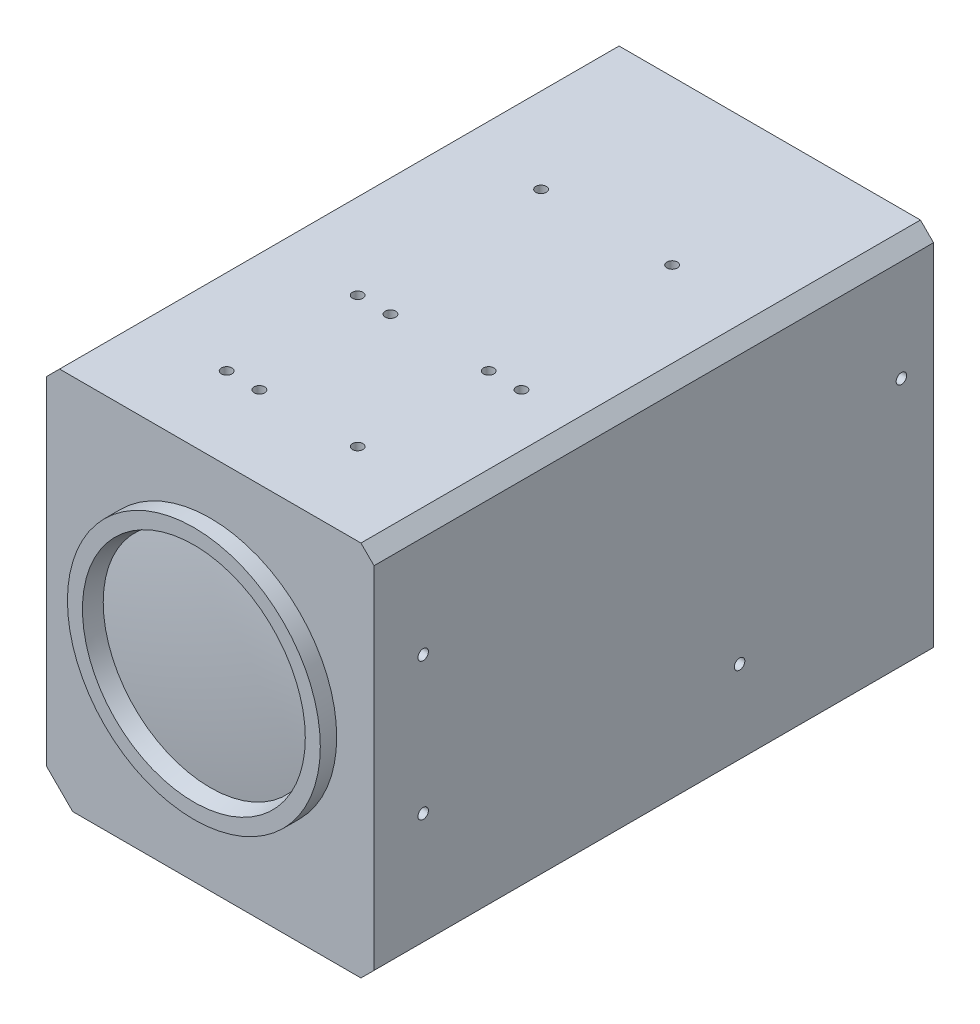
SolidWorks part; units mm, degrees
ref_plane "Front Plane" through (0, 0, 0) normal (0, 0, 1) x (1, 0, 0)
ref_plane "Top Plane" through (0, 0, 0) normal (0, 1, 0) x (1, 0, 0)
ref_plane "Right Plane" through (0, 0, 0) normal (1, 0, 0) x (0, 0, -1)
sketch "Sketch1" plane through (0, 0, 0) normal (0, 0, 1) x (1, 0, 0)
  line L0 (-25, 25.5) -> (-23, 27.5)
  line L1 (-21, -30) -> (23, -30)
  line L2 (-25, -26) -> (-25, 25.5)
  line L3 (-23, 27.5) -> (23, 27.5)
  line L4 (25, -28) -> (25, 25.5)
  line L5 (23, 27.5) -> (25, 25.5)
  line L6 (23, -30) -> (25, -28)
  line L7 (-25, -26) -> (-21, -30)
  point P0 (0, 0)
  point P1 (25, 27.5)
  point P2 (-25, -30)
  point P3 (-25, 27.5)
  point P4 (25, -30)
  dimension "D1" = 57.5
  dimension "D2" = 50
  dimension "D3" = 30
  dimension "D4" = 25
extrude "Boss-Extrude1" add sketch "Sketch1" along normal blind 85.4
sketch "Sketch2" plane through (0, 0, 85.4) normal (0, 0, 1) x (1, 0, 0)
  circle A0 centre (0, 0) radius 19.3
  circle A1 centre (0, 0) radius 17.008
  dimension "D1" = 38.6
  dimension "D2" = 34.016
extrude "Boss-Extrude2" add sketch "Sketch2" along normal blind 2.5
draft "Draft1" type of draft neutral plane draft angle 15 faces to draft 1 face at (17.008, 0, 87.9) neutral plane through (0, 0, 87.9) neutral plane normal (0, 0, 1) parameters "D1"=15
dome "Dome1" faces to dome 1 distance 1 reverse direction no elliptical dome no face at (-16.3381, 0, 85.4) parameters "D1"=1
hole_wizard "1/4 Clearance Hole1" positions "Sketch5" profile "Sketch4" hole size "1/4" standard "Ansi Inch"
sketch "Sketch5" plane through (0, -30, 0) normal (0, -1, 0) x (1, 0, 0)
  line L0 (25, 85.4) -> (25, 0) construction
  line L1 (19.3, 87.9) -> (-19.3, 87.9) construction
  point P0 (0, 67.9)
  dimension "D1" = 25
  dimension "D2" = 20
sketch "Sketch4" plane through (0, -30, 67.9) normal (1, 0, 0) x (0, 0, -1)
  line L0 (0, 0) -> (0, 10.0298)
  line L1 (0, 10.0298) -> (3.3782, 8)
  line L2 (3.3782, 8) -> (3.3782, 0)
  line L5 (3.3782, 0) -> (0, 0)
  line L10 (0, 10.0298) -> (-3.3782, 8) construction
  line L11 (0, -6.35) -> (0, 107.95) construction
  dimension "Hole Dia." = 6.7564
  dimension "Hole Depth" = 8
  dimension "Drill Angle" = 118
hole_wizard "M2x0.4 Tapped Hole1" positions "Sketch7" profile "Sketch6" tap size "M2x0.4" standard "ANSI Metric"
sketch "Sketch7" plane through (0, -30, 0) normal (0, -1, 0) x (-1, 0, 0)
  line L0 (0, -85.4) -> (0, 0) construction
  line L2 (21, -85.4) -> (-23, -85.4) construction
  line L3 (21, 0) -> (-23, 0) construction
  line L4 (-19.3, -87.9) -> (19.3, -87.9) construction
  point P12 (-8, -51.9)
  point P14 (8, -51.9)
  point P16 (-8, -22.9)
  point P18 (8, -22.9)
  point P24 (13.5, -47.7)
  point P26 (-13.5, -47.7)
  point P28 (-13.5, -14.7)
  point P30 (13.5, -14.7)
  dimension "D1" = 16
  dimension "D2" = 29
  dimension "D3" = 36
  dimension "D4" = 8
  dimension "D5" = 27
  dimension "D6" = 13.5
  dimension "D7" = 40.2
  dimension "D8" = 33
sketch "Sketch6" plane through (8, -30, 51.9) normal (1, 0, 0) x (0, 0, -1)
  line L0 (0, 0) -> (0, 2.4807)
  line L1 (0, 2.4807) -> (0.8, 2)
  line L2 (0.8, 2) -> (0.8, 0)
  line L5 (0.8, 0) -> (0, 0)
  line L10 (0, 2.4807) -> (-0.8, 2) construction
  line L11 (0, -6.35) -> (0, 107.95) construction
  dimension "Tap Drill Dia." = 1.6
  dimension "Tap Drill Depth" = 2
  dimension "Drill Angle" = 118
hole_wizard "M2x0.4 Tapped Hole2" positions "Sketch9" profile "Sketch8" tap size "M2x0.4" standard "ANSI Metric"
sketch "Sketch9" plane through (25, 0, 0) normal (1, 0, 0) x (0, 0, -1)
  line L0 (-87.9, 0) -> (0, 0) construction
  line L1 (-87.9, 19.3) -> (-87.9, -19.3) construction
  line L3 (0, -28) -> (0, 25.5) construction
  point P0 (-77.9, 10)
  point P2 (-77.9, -11)
  point P4 (-4.9, 10)
  point P6 (-29.6, -15.4)
  dimension "D1" = 21
  dimension "D2" = 10
  dimension "D3" = 25.4
  dimension "D4" = 48.3
  dimension "D5" = 73
  dimension "D6" = 10
sketch "Sketch8" plane through (25, 10, 77.9) normal (0, 1, 0) x (0, 0, -1)
  line L0 (0, 0) -> (0, 3.6807)
  line L1 (0, 3.6807) -> (0.8, 3.2)
  line L2 (0.8, 3.2) -> (0.8, 0)
  line L5 (0.8, 0) -> (0, 0)
  line L10 (0, 3.6807) -> (-0.8, 3.2) construction
  line L11 (0, -6.35) -> (0, 107.95) construction
  dimension "Tap Drill Dia." = 1.6
  dimension "Tap Drill Depth" = 3.2
  dimension "Drill Angle" = 118
hole_wizard "M2x0.4 Tapped Hole3" positions "Sketch11" profile "Sketch10" tap size "M2x0.4" standard "ANSI Metric"
sketch "Sketch11" plane through (0, 27.5, 0) normal (0, 1, 0) x (1, 0, 0)
  line L0 (0, 0) -> (0, -87.9) construction
  line L1 (-19.3, -87.9) -> (19.3, -87.9) construction
  point P0 (-5, -72.9)
  point P4 (15, -52.9)
  point P6 (-5, -52.9)
  point P16 (-10, -72.9)
  point P18 (10, -72.9)
  point P20 (10, -52.9)
  point P22 (-10, -52.9)
  point P29 (-10, -24.9)
  point P31 (10, -24.9)
  dimension "D1" = 20
  dimension "D2" = 15
  dimension "D3" = 5
  dimension "D4" = 20
  dimension "D5" = 20
  dimension "D6" = 10
  dimension "D7" = 28
sketch "Sketch10" plane through (-5, 27.5, 72.9) normal (1, 0, 0) x (0, 0, 1)
  line L0 (0, 0) -> (0, 3.6807)
  line L1 (0, 3.6807) -> (0.8, 3.2)
  line L2 (0.8, 3.2) -> (0.8, 0)
  line L5 (0.8, 0) -> (0, 0)
  line L10 (0, 3.6807) -> (-0.8, 3.2) construction
  line L11 (0, -6.35) -> (0, 107.95) construction
  dimension "Tap Drill Dia." = 1.6
  dimension "Tap Drill Depth" = 3.2
  dimension "Drill Angle" = 118
hole_wizard "M2x0.4 Tapped Hole4" positions "Sketch13" profile "Sketch12" tap size "M2x0.4" standard "ANSI Metric"
sketch "Sketch13" plane through (-25, 0, 0) normal (-1, 0, 0) x (0, 0, 1)
  line L0 (0, 0) -> (87.9, 0) construction
  line L1 (87.9, -19.3) -> (87.9, 19.3) construction
  point P8 (2.7, 4.5)
  point P10 (2.7, -9.5)
  dimension "D1" = 14
  dimension "D2" = 4.5
  dimension "D3" = 85.2
sketch "Sketch12" plane through (-25, 4.5, 2.7) normal (0, 1, 0) x (0, 0, 1)
  line L0 (0, 0) -> (0, 3.6807)
  line L1 (0, 3.6807) -> (0.8, 3.2)
  line L2 (0.8, 3.2) -> (0.8, 0)
  line L5 (0.8, 0) -> (0, 0)
  line L10 (0, 3.6807) -> (-0.8, 3.2) construction
  line L11 (0, -6.35) -> (0, 107.95) construction
  dimension "Tap Drill Dia." = 1.6
  dimension "Tap Drill Depth" = 3.2
  dimension "Drill Angle" = 118
